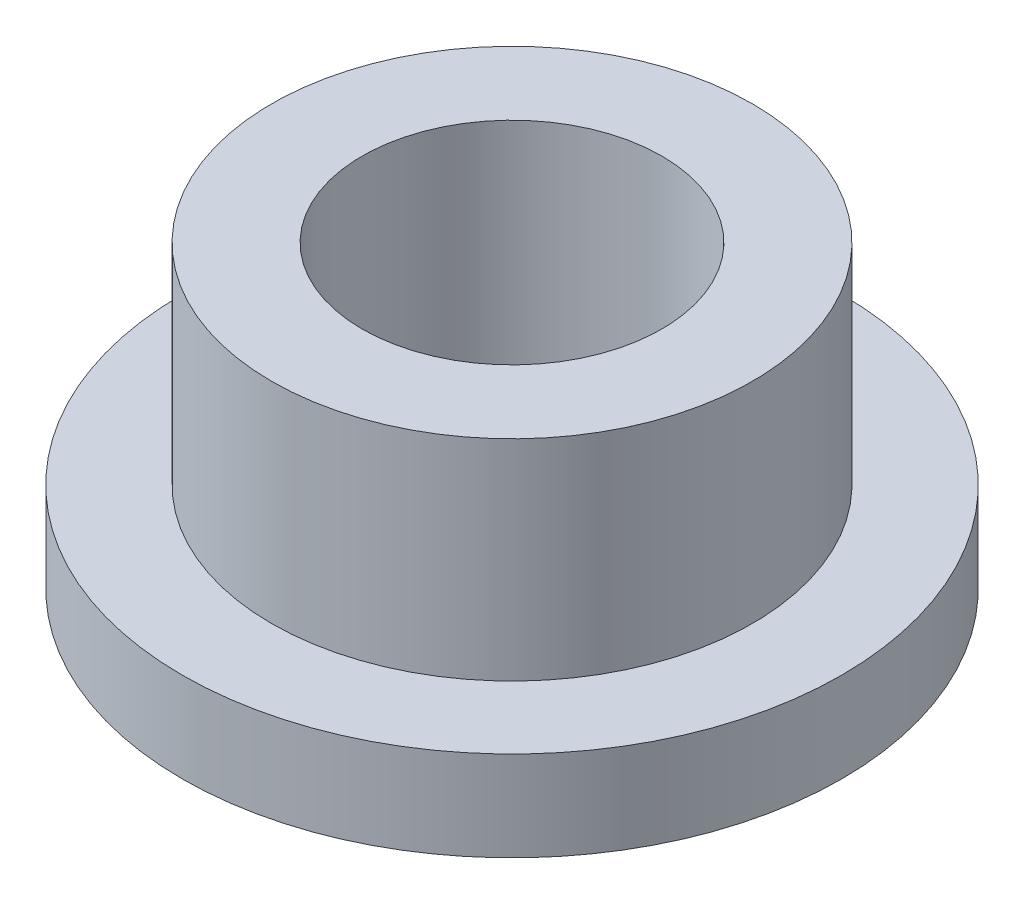
SolidWorks part; units mm, degrees
ref_plane "Front" through (0, 0, 0) normal (0, 0, 1) x (1, 0, 0)
ref_plane "Top" through (0, 0, 0) normal (0, 1, 0) x (1, 0, 0)
ref_plane "Right" through (0, 0, 0) normal (1, 0, 0) x (0, 0, -1)
sketch "Sketch1" plane through (0, 0, 0) normal (0, 1, 0) x (1, 0, 0)
  circle A0 centre (0, 0) radius 2.5
  circle A1 centre (0, 0) radius 4.01
  circle A2 centre (0, 0) radius 5.5
  dimension "ID" = 5
  dimension "OD" = 8.02
  dimension "FlangeOD" = 11
sketch "Sketch2" plane through (0, 0, 0) normal (0, 1, 0) x (1, 0, 0)
  circle A0 centre (0, 0) radius 2.5 construction
  circle A1 centre (0, 0) radius 4.01 construction
  circle A2 centre (0, 0) radius 2.5
  circle A3 centre (0, 0) radius 4.01
extrude "Boss-Extrude1" add sketch "Sketch2" along normal blind 5
sketch "Sketch3" plane through (0, 0, 0) normal (0, 1, 0) x (1, 0, 0)
  circle A0 centre (0, 0) radius 5.5 construction
  circle A1 centre (0, 0) radius 4.01 construction
  circle A2 centre (0, 0) radius 5.5
  circle A3 centre (0, 0) radius 4.01
extrude "Boss-Extrude2" add sketch "Sketch3" along normal blind 1.5
ref_axis "Center Axis 1" through (0, 5, 0) along (0, -1, 0)
